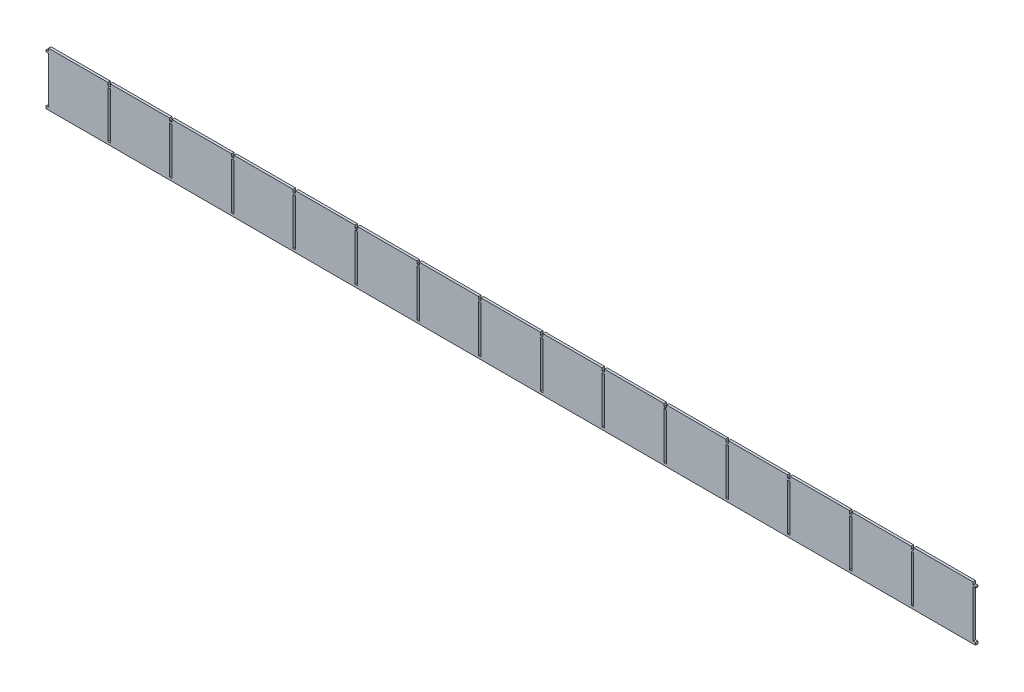
SolidWorks part; units mm, degrees
material "Cedar"
ref_plane "Front Plane" through (0, 0, 0) normal (0, 0, 1) x (1, 0, 0)
ref_plane "Top Plane" through (0, 0, 0) normal (0, 1, 0) x (1, 0, 0)
ref_plane "Right Plane" through (0, 0, 0) normal (1, 0, 0) x (0, 0, -1)
sketch "Sketch2" plane through (0, 0, 0) normal (0, 0, 1) x (1, 0, 0)
  line L0 (-752, 38.991) -> (-752, 36.298)
  line L1 (-752, 36.298) -> (-748, 36.298)
  line L2 (-748, 36.298) -> (-748, -39.4016)
  line L3 (-748, -39.4016) -> (-752, -39.4016)
  line L4 (-752, -39.4016) -> (-752, -43.4016)
  line L5 (-752, -43.4016) -> (752, -43.4016)
  line L6 (752, -43.4016) -> (752, -39.4016)
  line L7 (752, -39.4016) -> (748, -39.4016)
  line L8 (748, -39.4016) -> (748, 36.298)
  line L9 (748, 36.298) -> (752, 36.298)
  line L10 (748, 43.4016) -> (748, 38.991)
  line L11 (748, 43.4016) -> (652, 43.4016)
  line L12 (648, 43.4016) -> (652, 43.4016) construction
  line L13 (552, 43.4016) -> (548, 43.4016) construction
  line L14 (452, 43.4016) -> (448, 43.4016) construction
  line L15 (352, 43.4016) -> (348, 43.4016) construction
  line L16 (252, 43.4016) -> (248, 43.4016) construction
  line L17 (152, 43.4016) -> (148, 43.4016) construction
  line L18 (52, 43.4016) -> (48, 43.4016) construction
  line L19 (-48, 43.4016) -> (-52, 43.4016) construction
  line L20 (-148, 43.4016) -> (-152, 43.4016) construction
  line L21 (-152, 43.4016) -> (-248, 43.4016) construction
  line L22 (-248, 43.4016) -> (-252, 43.4016) construction
  line L23 (-348, 43.4016) -> (-352, 43.4016) construction
  line L24 (-448, 43.4016) -> (-452, 43.4016) construction
  line L25 (-548, 43.4016) -> (-552, 43.4016) construction
  line L26 (-648, 43.4016) -> (-652, 43.4016) construction
  line L27 (-748, 43.4016) -> (-752, 43.4016) construction
  line L28 (748, 38.991) -> (752, 38.991)
  line L29 (752, 38.991) -> (752, 36.298)
  line L30 (652, 36.298) -> (652, -39.4016)
  line L31 (652, -39.4016) -> (648, -39.4016)
  line L32 (648, -39.4016) -> (648, 36.298)
  line L33 (652, 43.4016) -> (652, 38.991)
  line L34 (652, 38.991) -> (650.1, 38.991)
  line L35 (648, 38.991) -> (648, 43.4016)
  line L36 (648, 43.4016) -> (552, 43.4016)
  line L37 (552, 43.4016) -> (552, 38.991)
  line L38 (650.1, 38.991) -> (650.1, 36.298)
  line L39 (650.1, 36.298) -> (652, 36.298)
  line L40 (652, 36.298) -> (651.9607, 36.2766)
  line L41 (552, 36.298) -> (552, -39.4016)
  line L42 (552, -39.4016) -> (548, -39.4016)
  line L43 (548, -39.4016) -> (548, 36.298)
  line L44 (648, 38.991) -> (649.9, 38.991)
  line L45 (649.9, 38.991) -> (649.9, 36.298)
  line L46 (548, 38.991) -> (548, 43.4016)
  line L47 (548, 43.4016) -> (452, 43.4016)
  line L48 (452, 43.4016) -> (452, 38.991)
  line L49 (649.9, 36.298) -> (648, 36.298)
  line L50 (648, 36.298) -> (648.0347, 36.3099)
  line L51 (548, 38.991) -> (549.9, 38.991)
  line L52 (452, 36.298) -> (452, -39.4016)
  line L53 (452, -39.4016) -> (448, -39.4016)
  line L54 (448, -39.4016) -> (448, 36.298)
  line L55 (549.9, 38.991) -> (549.9, 36.298)
  line L56 (549.9, 36.298) -> (548, 36.298)
  line L57 (448, 38.991) -> (448, 43.4016)
  line L58 (448, 43.4016) -> (352, 43.4016)
  line L59 (352, 43.4016) -> (352, 38.991)
  line L60 (548, 36.298) -> (548.084, 36.3217)
  line L61 (552, 38.991) -> (550.1, 38.991)
  line L62 (550.1, 38.991) -> (550.1, 36.298)
  line L63 (352, 36.298) -> (352, -39.4016)
  line L64 (352, -39.4016) -> (350, -39.4016)
  line L65 (350, -39.4016) -> (348, -39.4016)
  line L66 (348, -39.4016) -> (348, 36.298)
  line L67 (550.1, 36.298) -> (552, 36.298)
  line L68 (452, 38.991) -> (450.1, 38.991)
  line L69 (348, 38.991) -> (348, 43.4016)
  line L70 (348, 43.4016) -> (252, 43.4016)
  line L71 (252, 43.4016) -> (252, 38.991)
  line L72 (450.1, 38.991) -> (450.1, 36.298)
  line L73 (450.1, 36.298) -> (452, 36.298)
  line L74 (448, 38.991) -> (449.9, 38.991)
  line L75 (252, 36.298) -> (252, -39.4016)
  line L76 (252, -39.4016) -> (250, -39.4016)
  line L77 (250, -39.4016) -> (248, -39.4016)
  line L78 (248, -39.4016) -> (248, 36.298)
  line L79 (449.9, 38.991) -> (449.9, 36.298)
  line L80 (449.9, 36.298) -> (448, 36.298)
  line L81 (248, 38.991) -> (248, 43.4016)
  line L82 (248, 43.4016) -> (152, 43.4016)
  line L83 (152, 43.4016) -> (152, 38.991)
  line L84 (352, 38.991) -> (350.1, 38.991)
  line L85 (350.1, 38.991) -> (350.1, 36.298)
  line L86 (350.1, 36.298) -> (352, 36.298)
  line L87 (152, 36.298) -> (152, -39.4016)
  line L88 (152, -39.4016) -> (148, -39.4016)
  line L89 (148, -39.4016) -> (148, 36.298)
  line L90 (348, 38.991) -> (349.9, 38.991)
  line L91 (349.9, 38.991) -> (349.9, 36.298)
  line L92 (148, 38.991) -> (148, 43.4016)
  line L93 (148, 43.4016) -> (52, 43.4016)
  line L94 (52, 43.4016) -> (52, 38.991)
  line L95 (349.9, 36.298) -> (348, 36.298)
  line L96 (248, 38.991) -> (249.9, 38.991)
  line L97 (249.9, 38.991) -> (249.9, 36.298)
  line L98 (52, 36.298) -> (52, -39.4016)
  line L99 (52, -39.4016) -> (48, -39.4016)
  line L100 (48, -39.4016) -> (48, 36.298)
  line L101 (249.9, 36.298) -> (248, 36.298)
  line L102 (252, 38.991) -> (250.1, 38.991)
  line L103 (48, 38.991) -> (48, 43.4016)
  line L104 (48, 43.4016) -> (-48, 43.4016)
  line L105 (-48, 43.4016) -> (-48, 38.991)
  line L106 (250.1, 38.991) -> (250.1, 36.298)
  line L107 (250.1, 36.298) -> (252, 36.298)
  line L108 (152, 38.991) -> (150.1, 38.991)
  line L109 (-48, 36.298) -> (-48, -39.4016)
  line L110 (-48, -39.4016) -> (-52, -39.4016)
  line L111 (-52, -39.4016) -> (-52, 36.298)
  line L112 (150.1, 38.991) -> (150.1, 36.298)
  line L113 (150.1, 36.298) -> (152, 36.298)
  line L114 (-52, 38.991) -> (-52, 43.4016)
  line L115 (-52, 43.4016) -> (-148, 43.4016)
  line L116 (-148, 43.4016) -> (-148, 38.991)
  line L117 (-152, 38.991) -> (-150.1, 38.991)
  line L118 (-150.1, 38.991) -> (-150.1, 36.298)
  line L119 (-150.1, 36.298) -> (-152, 36.298)
  line L120 (-148, 36.298) -> (-148, -39.4016)
  line L121 (-148, 36.298) -> (-149.9, 36.298)
  line L122 (-148, -39.4016) -> (-152, -39.4016)
  line L123 (-152, 43.4016) -> (-152, 38.991)
  line L124 (-152, 43.4016) -> (-248, 43.4016)
  line L125 (-248, 43.4016) -> (-248, 38.991)
  line L126 (-248, 38.991) -> (-249.9, 38.991)
  line L127 (-249.9, 38.991) -> (-249.9, 36.298)
  line L128 (-249.9, 36.298) -> (-248, 36.298)
  line L129 (-248, 36.298) -> (-248, -39.4016)
  line L130 (-248, -39.4016) -> (-252, -39.4016)
  line L131 (-252, -39.4016) -> (-252, 36.298)
  line L132 (-252, 36.298) -> (-250.1, 36.298)
  line L133 (-250.1, 36.298) -> (-250.1, 38.991)
  line L134 (-252, 38.991) -> (-252, 43.4016)
  line L135 (-252, 43.4016) -> (-348, 43.4016)
  line L136 (-348, 43.4016) -> (-348, 38.991)
  line L137 (-352, 38.991) -> (-350.1, 38.991)
  line L138 (-350.1, 38.991) -> (-350.1, 36.298)
  line L139 (-350.1, 36.298) -> (-352, 36.298)
  line L140 (-348, 36.298) -> (-348, -39.4016)
  line L141 (-348, -39.4016) -> (-352, -39.4016)
  line L142 (-352, -39.4016) -> (-352, 36.298)
  line L143 (-348, 38.991) -> (-349.9, 38.991)
  line L144 (-349.9, 38.991) -> (-349.9, 36.298)
  line L145 (-352, 38.991) -> (-352, 43.4016)
  line L146 (-352, 43.4016) -> (-448, 43.4016)
  line L147 (-448, 43.4016) -> (-448, 38.991)
  line L148 (-448, 38.991) -> (-449.9, 38.991)
  line L149 (-449.9, 38.991) -> (-449.9, 36.298)
  line L150 (-449.9, 36.298) -> (-448, 36.298)
  line L151 (-448, 36.298) -> (-448, -39.4016)
  line L152 (-448, -39.4016) -> (-452, -39.4016)
  line L153 (-452, -39.4016) -> (-452, 36.298)
  line L154 (-452, 36.298) -> (-450.1, 36.298)
  line L155 (-450.1, 36.298) -> (-450.1, 38.991)
  line L156 (-450.1, 38.991) -> (-452, 38.991)
  line L157 (-452, 38.991) -> (-452, 43.4016)
  line L158 (-452, 43.4016) -> (-548, 43.4016)
  line L159 (-548, 43.4016) -> (-548, 38.991)
  line L160 (-548, 38.991) -> (-549.9, 38.991)
  line L161 (-549.9, 38.991) -> (-549.9, 36.298)
  line L162 (-549.9, 36.298) -> (-548, 36.298)
  line L163 (-548, 36.298) -> (-548, -39.4016)
  line L164 (-548, -39.4016) -> (-552, -39.4016)
  line L165 (-552, -39.4016) -> (-552, 36.298)
  line L166 (-552, 36.298) -> (-550.1, 36.298)
  line L167 (-550.1, 36.298) -> (-550.1, 38.991)
  line L168 (-550.1, 38.991) -> (-552, 38.991)
  line L169 (-552, 38.991) -> (-552, 43.4016)
  line L170 (-552, 43.4016) -> (-648, 43.4016)
  line L171 (-648, 43.4016) -> (-648, 38.991)
  line L172 (-648, 38.991) -> (-649.9, 38.991)
  line L173 (-649.9, 38.991) -> (-649.9, 36.298)
  line L174 (-649.9, 36.298) -> (-648, 36.298)
  line L175 (-648, 36.298) -> (-648, -39.4016)
  line L176 (-648, -39.4016) -> (-652, -39.4016)
  line L177 (-652, -39.4016) -> (-652, 36.298)
  line L178 (-652, 36.298) -> (-650.1, 36.298)
  line L179 (-650.1, 36.298) -> (-650.1, 38.991)
  line L180 (-650.1, 38.991) -> (-652, 38.991)
  line L181 (-652, 38.991) -> (-652, 43.4016)
  line L182 (-652, 43.4016) -> (-748, 43.4016)
  line L183 (-748, 43.4016) -> (-748, 38.991)
  line L184 (-748, 38.991) -> (-752, 38.991)
  line L185 (-752, 36.298) -> (-748, 36.298)
  line L186 (-748, -39.4016) -> (-752, -39.4016)
  line L187 (-349.9, 36.298) -> (-348, 36.298)
  line L188 (-250.1, 38.991) -> (-252, 38.991)
  line L189 (-149.9, 36.298) -> (-149.9, 38.991)
  line L190 (-149.9, 38.991) -> (-148, 38.991)
  line L191 (148, 38.991) -> (149.9, 38.991)
  line L192 (149.9, 38.991) -> (149.9, 36.298)
  line L193 (149.9, 36.298) -> (148, 36.298)
  line L194 (52, 38.991) -> (50.1, 38.991)
  line L195 (50.1, 38.991) -> (50.1, 36.298)
  line L196 (50.1, 36.298) -> (52, 36.298)
  line L197 (48, 38.991) -> (49.9, 38.991)
  line L198 (49.9, 38.991) -> (49.9, 36.298)
  line L199 (49.9, 36.298) -> (48, 36.298)
  line L200 (-48, 38.991) -> (-49.9, 38.991)
  line L201 (-49.9, 38.991) -> (-49.9, 36.298)
  line L202 (-49.9, 36.298) -> (-48, 36.298)
  line L203 (-52, 38.991) -> (-50.1, 38.991)
  line L204 (-50.1, 38.991) -> (-50.1, 36.298)
  line L205 (-50.1, 36.298) -> (-52, 36.298)
  line L206 (-152, 36.298) -> (-152, -39.4016)
  point P184 (-650, 43.4016)
  point P191 (-550, 43.4016)
  point P192 (-450, 43.4016)
  point P193 (-350, 43.4016)
  point P194 (-250, 43.4016)
  point P195 (-150, 43.4016)
  point P196 (-50, 43.4016)
  point P197 (50, 43.4016)
  point P198 (150, 43.4016)
  point P199 (250, 43.4016)
  point P200 (350, 43.4016)
  point P201 (450, 43.4016)
  point P202 (550, 43.4016)
  point P203 (650, 43.4016)
extrude "Boss-Extrude1" add sketch "Sketch2" along normal blind 4 contours L206 L119 L118 L117 L123 L124 L125 L126 L127 L128 L129 L130 L131 L132 L133 L188 L134 L135 L136 L143 L144 L187 L140 L141 L142 L139 L138 L137 L145 L146 L147 L148 L149 L150 L151 L152 L153 L154 L155 L156 L157 L158 L159 L160 L161 L162 L163 L164 L165 L166 L167 region at (0, -0.035, 0)
sketch "Sketch3" plane through (0, 0, 4) normal (0, 0, 1) x (1, 0, 0)
  line L0 (-776.0978, 15.2516) -> (-721.0168, 15.2516) construction
  line L1 (-652, 43.4016) -> (-748, 43.4016) construction
  dimension "D1" = 28.15
